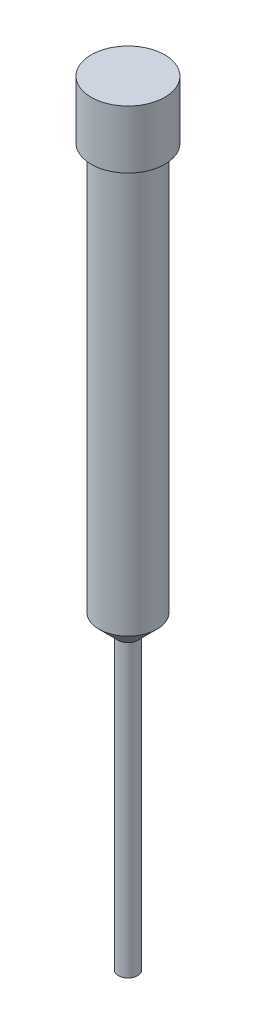
SolidWorks part; units mm, degrees
ref_plane "Front Plane" through (0, 0, 0) normal (0, 0, 1) x (1, 0, 0)
ref_plane "Top Plane" through (0, 0, 0) normal (0, 1, 0) x (1, 0, 0)
ref_plane "Right Plane" through (0, 0, 0) normal (1, 0, 0) x (0, 0, -1)
sketch "Sketch3" plane through (0, 0, 0) normal (0, 1, 0) x (1, 0, 0)
  line L0 (0, 0) -> (0, -20049.4382) construction
  line L1 (0, 0) -> (20049.4382, 0) construction
  circle A0 centre (0, 0) radius 0.5
  dimension "D1" = 1
extrude "Boss-Extrude4" add sketch "Sketch3" along normal blind 25
sketch "Orientation Sketch" plane through (0, 0, 0) normal (0, -1, 0) x (-1, 0, 0)
  circle A0 centre (0, 0) radius 0.5 construction
  circle A1 centre (0, 0) radius 0.5
  point P3 (0, 0)
other "FormTool1"
sketch "Sketch5" plane through (0, 25, 0) normal (0, 1, 0) x (1, 0, 0)
  circle A3 centre (0, 0) radius 1.5
  dimension "D1" = 3
extrude "Boss-Extrude5" add sketch "Sketch5" along normal blind 15
chamfer "Chamfer2" distance 10 angle 45 1 edges at (0, 25, 0.5)
sketch "Sketch6" plane through (0, 40, 0) normal (0, 1, 0) x (1, 0, 0)
  circle A0 centre (0, 0) radius 1.9007
  dimension "D1" = 3.8013
extrude "Boss-Extrude6" add sketch "Sketch6" against normal blind 3
